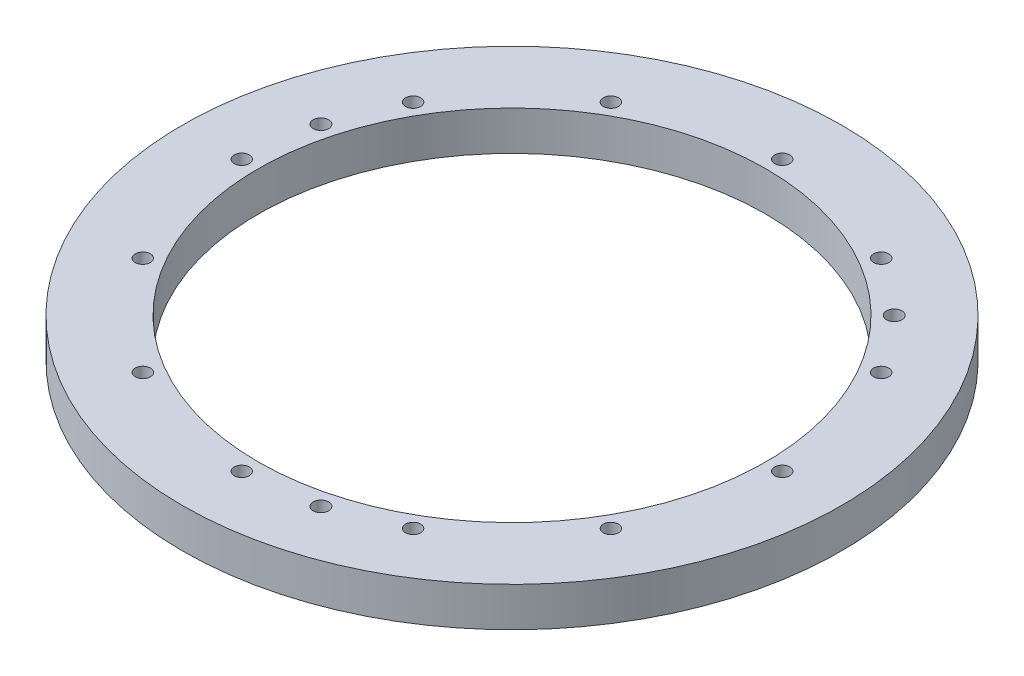
SolidWorks part; units mm, degrees
material "6061 Alloy"
ref_plane "Front Plane" through (0, 0, 0) normal (0, 0, 1) x (1, 0, 0)
ref_plane "Top Plane" through (0, 0, 0) normal (0, 1, 0) x (1, 0, 0)
ref_plane "Right Plane" through (0, 0, 0) normal (1, 0, 0) x (0, 0, -1)
sketch "Sketch1" plane through (0, 0, 0) normal (0, 1, 0) x (1, 0, 0)
  circle A0 centre (0, 0) radius 49.2125
  circle A1 centre (0, 0) radius 63.881
  circle A3 centre (0, -52.3875) radius 1.4732
  circle A4 centre (-26.1938, -45.3689) radius 1.4732
  circle A5 centre (-45.3689, -26.1937) radius 1.4732
  circle A6 centre (-52.3875, 0) radius 1.4732
  circle A7 centre (-45.3689, 26.1938) radius 1.4732
  circle A8 centre (-26.1937, 45.3689) radius 1.4732
  circle A9 centre (0, 52.3875) radius 1.4732
  circle A10 centre (26.1938, 45.3689) radius 1.4732
  circle A11 centre (45.3689, 26.1937) radius 1.4732
  circle A12 centre (52.3875, 0) radius 1.4732
  circle A13 centre (45.3689, -26.1938) radius 1.4732
  circle A14 centre (26.1937, -45.3689) radius 1.4732
  point P21 (0, 0)
  dimension "D1" = 98.425
  dimension "D4" = 2.9464
  dimension "D5" = 52.3875
  dimension "D2" = 14.6685
  dimension "D6" = 12
extrude "Boss-Extrude1" add sketch "Sketch1" along normal blind 7.62 contours A0 | A1 region at (-62.0742, 0, 0)
sketch "Sketch2" plane through (0, 7.62, 0) normal (0, 1, 0) x (1, 0, 0)
  circle A0 centre (-45.3689, 26.1938) radius 1.4732 construction
  circle A1 centre (-52.3875, 0) radius 1.4732 construction
  circle A2 centre (-45.3689, 26.1938) radius 1.4732 construction
  circle A3 centre (-52.3875, 0) radius 1.4732 construction
  arc A4 (-52.3875, 0) -> (-45.3689, 26.1938) centre (0, 0) cw construction
  circle A5 centre (-50.6024, 13.5589) radius 1.5
  dimension "D1" = 3
extrude "Cut-Extrude1" cut sketch "Sketch2" against normal through all
pattern_circular "CirPattern1" count 3 over 360 about axis through (0, 7.62, 0) along (0, 1, 0) of "Cut-Extrude1"
equation "\"Middle Coupler Inner Daimeter\"= 3.875in"
equation "\"Middle Coupler  Wall Thickness\" = 0.25in"
equation "\"Middle Coupler Bottom Thickness\"= 0.2in"
equation "\"Bearing Rail Offset\"= 0.45in"
equation "\"3-56 UNF Tap\"= 0.089in"
equation "\"3-56 UNF Clearance\"= 0.104in"
equation "\"D5@Sketch1\"=(\"Middle Coupler Inner Daimeter\"*2+0.5)/4in"
equation "\"Ball Bearing Distance\"= 0.03in"
equation "\"D4@Sketch1\"=\"4-40 Clearance\""
equation "\"D1@Sketch1\"=\"Middle Coupler Inner Daimeter\""
equation "\"TCA Outer Diameter\" = 6in"
equation "\"Interstage Aeroframe Wall Thickness\" = 0.072in"
equation "\"Compression Spring OD\"= 0.42in"
equation "\"10-24 Tap\"= 0.157in"
equation "\"10-24 Clearance\"= 0.196in"
equation "\"Lower Stage Fuselage Wall Thickness\" = 0.25in"
equation "\"6-32 Tap\" = 0.107in"
equation "\"1/4-20 Tap\" = 0.201in"
equation "\"D2@Sketch1\"=0.5875 - 10/1000"
equation "\"D1@Sketch2\"=3mm"
equation "\"3-48 Tap\"= 0.079in"
equation "\"4-40 Tap\"= 0.089in"
equation "\"3-48 Clearance\" = 0.104in"
equation "\"4-40 Clearance\" = 0.116in"
equation "\"6-32 Clearance\" = 0.144"
equation "\"12-24 Tap\" = 0.177in"
equation "\"12-24 Major Diameter\"= 0.216in"
